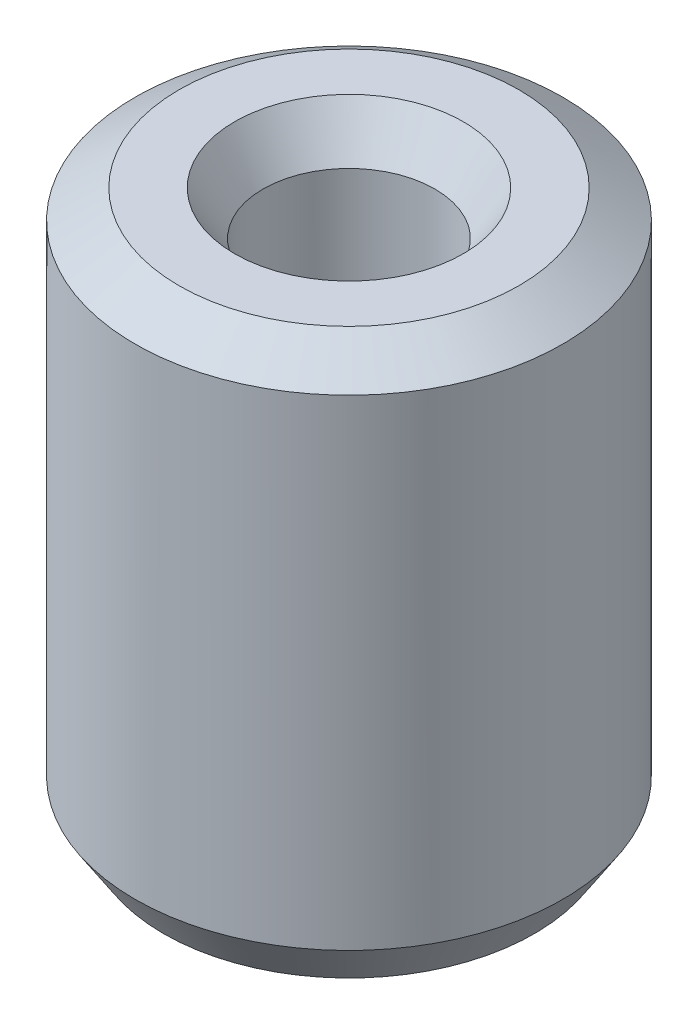
SolidWorks part; units mm, degrees
ref_plane "Front Plane" through (0, 0, 0) normal (0, 0, 1) x (1, 0, 0)
ref_plane "Top Plane" through (0, 0, 0) normal (0, 1, 0) x (1, 0, 0)
ref_plane "Right Plane" through (0, 0, 0) normal (1, 0, 0) x (0, 0, -1)
sketch "Sketch1" plane through (0, 0, 0) normal (0, 1, 0) x (1, 0, 0)
  circle A0 centre (0, 0) radius 17.5
  dimension "SLEEVE_OD" = 35
extrude "Boss-Extrude1" add sketch "Sketch1" along normal blind 45.2807
sketch "Sketch2" plane through (0, 0, 0) normal (0, 1, 0) x (1, 0, 0)
  circle A0 centre (0, 0) radius 7.0289
  dimension "BORE_D" = 14.0578
extrude "Cut-Extrude1" cut sketch "Sketch2" along normal through all
chamfer "Chamfer1" distance 2.331 angle 57.092 4 edges at (0, 45.2807, 7.0289) (0, 0, 7.0289) (0, 0, 17.5) (0, 45.2807, 17.5) first distance on face at (0, 45.2807, 7.0289) first distance on face at (0, 0, 7.0289) first distance on face at (0, 45.2807, 17.5)
